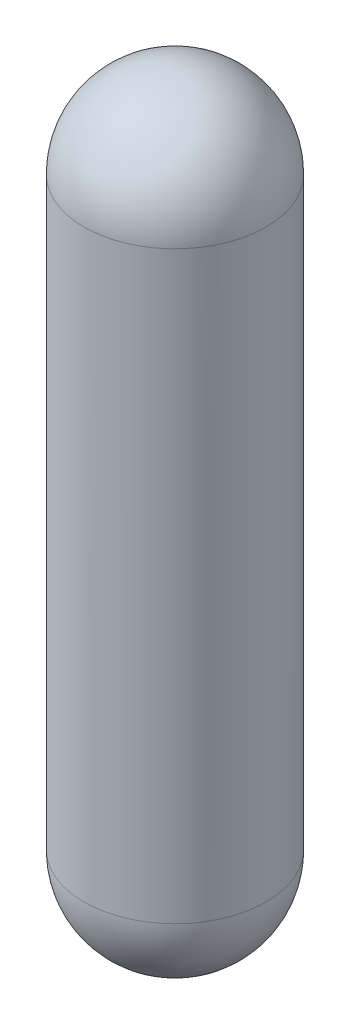
SolidWorks part; units mm, degrees
ref_plane "Front Plane" through (0, 0, 0) normal (0, 0, 1) x (1, 0, 0)
ref_plane "Top Plane" through (0, 0, 0) normal (0, 1, 0) x (1, 0, 0)
ref_plane "Right Plane" through (0, 0, 0) normal (1, 0, 0) x (0, 0, -1)
sketch "Sketch1" plane through (0, 0, 0) normal (0, 0, 1) x (1, 0, 0)
  line L0 (0, 1830) -> (0, 2115)
  line L2 (0, 0) -> (0, 1830)
  line L4 (285, 0) -> (285, 1830)
  line L5 (0, -285) -> (0, 0)
  line L6 (0, 976.2421) -> (285, 976.2421) construction
  arc A2 (285, 1830) -> (0, 2115) centre (0, 1830) ccw
  arc A3 (0, -285) -> (285, 0) centre (0, 0) ccw
  dimension "D1" = 2400
  dimension "D2" = 285
revolve "Revolve1" add sketch "Sketch1" angle 360 about L2
